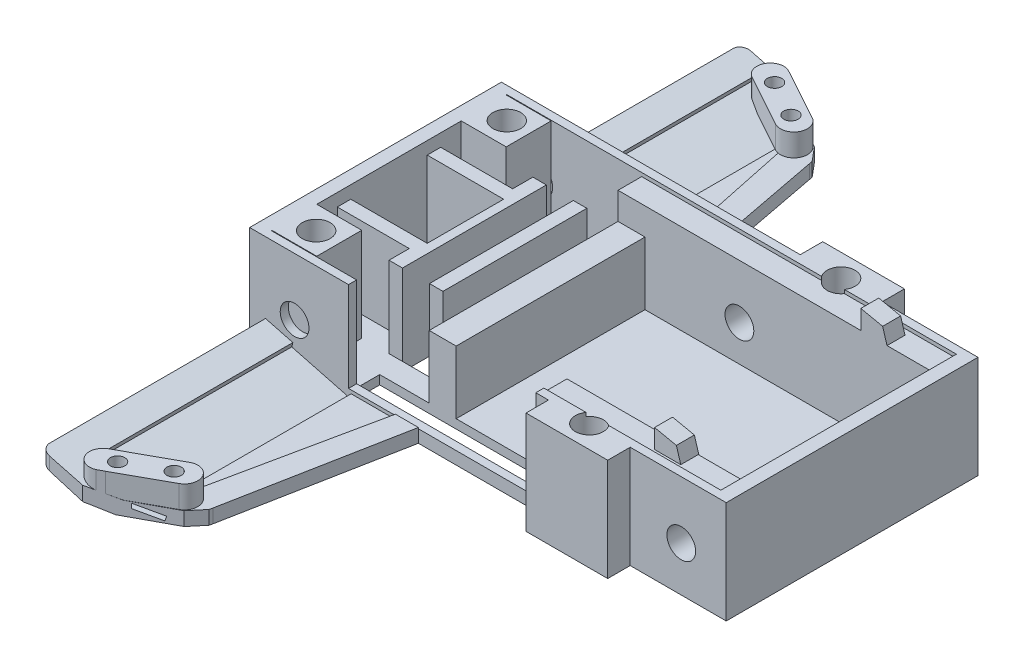
SolidWorks part; units mm, degrees
ref_plane "前视基准面" through (0, 0, 0) normal (0, 0, 1) x (1, 0, 0)
ref_plane "上视基准面" through (0, 0, 0) normal (0, 1, 0) x (1, 0, 0)
ref_plane "右视基准面" through (0, 0, 0) normal (1, 0, 0) x (0, 0, -1)
sketch "草图1" plane through (0, 0, 0) normal (0, 1, 0) x (1, 0, 0)
  line L1 (26.5, -14) -> (-26.5, -14)
  line L2 (26.5, -14) -> (26.5, 14)
  line L3 (26.5, 14) -> (-26.5, 14)
  line L4 (-26.5, -14) -> (-26.5, 14)
  line L5 (26.5, -14) -> (-26.5, 14) construction
  line L6 (26.5, 14) -> (-26.5, -14) construction
  line L7 (25, -13.1) -> (-25, -13.1)
  line L8 (25, -13.1) -> (25, 13.1)
  line L9 (25, 13.1) -> (-25, 13.1)
  line L10 (-25, -13.1) -> (-25, 13.1)
  line L11 (25, -13.1) -> (-25, 13.1) construction
  line L12 (25, 13.1) -> (-25, -13.1) construction
  line L16 (-25, 0.6) -> (-25, 1.6)
  point P0 (0, 0)
  point P6 (0, 0)
  dimension "D1" = 53
  dimension "D2" = 28
  dimension "D3" = 50
  dimension "D4" = 26.2
extrude "凸台-拉伸1" add sketch "草图1" along normal blind 10.4 contours L4 L1 L2 L3 L7 L10 L9 L8 region at (0, 0, 13.4006)
extrude "凸台-拉伸4" add sketch "草图1<3>" against normal blind 1 contours L10 L7 L8 L9 | L4 L1 L2 L3 L7 L10 L9 L8 | L10 region at (0, 0, 13.4006) region at (0, 0, 0)
sketch "草图1<3>" plane through (0, 0, 0) normal (0, 1, 0) x (1, 0, 0) same geometry as "草图1"
sketch "草图2" plane through (0, 0, 0) normal (1, 0, 0) x (0, 0, -1)
  line L0 (-1.6918, 0) -> (1.6918, 0)
  line L1 (1.6918, 0) -> (0.5135, 2.6035)
  line L2 (0.5135, 2.6035) -> (-0.5135, 2.6035)
  line L3 (13.1, 10.4) -> (13.1, 7.6355)
  line L4 (0, 3.9454) -> (0, 2.6035) construction
  line L5 (-1.6918, 0) -> (-0.5135, 2.6035)
  line L6 (0, 0) -> (0, -3.8405) construction
  line L7 (13.1, 7.6355) -> (10.1045, 9.7857)
  line L8 (13.1, 10.4) -> (13.1, 0) construction
  line L9 (10.1045, 9.7857) -> (10.1045, 10.4)
  line L10 (-14, 10.4) -> (14, 10.4) construction
  line L11 (10.1045, 10.4) -> (13.1, 10.4)
  line L12 (-13.1, 10.4) -> (-13.1, 7.6355)
  line L14 (-10.1045, 10.4) -> (-13.1, 10.4)
  line L15 (-10.1045, 9.7857) -> (-10.1045, 10.4)
  line L16 (-13.1, 7.6355) -> (-10.1045, 9.7857)
sketch "草图4" plane through (0, 0, 0) normal (0, 1, 0) x (1, 0, 0)
  line L1 (-12.25, 0) -> (37.6474, -0.075) construction
  line L2 (46.8944, -0.075) -> (20.0243, -0.075) construction
  line L3 (-10, 13.1) -> (-10, -13.1)
  line L4 (25, 10.4681) -> (-7, 10.4681)
  line L6 (25, -10.5319) -> (-7, -10.5319)
  line L7 (25, 13.1) -> (-25, 13.1) construction
  line L8 (-7, 10.4681) -> (-7, -10.5319)
  line L9 (25, 10.4681) -> (-7, -10.5319) construction
  line L10 (25, -10.5319) -> (-7, 10.4681) construction
  line L11 (25, -13.1) -> (-25, -13.1) construction
  line L12 (-10, 13.1) -> (25, 13.1)
  line L13 (25, 13.1) -> (25, 10.4681)
  line L14 (25, -10.5319) -> (25, -13.1)
  line L15 (25, -13.1) -> (-10, -13.1)
  point P4 (9, -0.0319)
  dimension "D1" = 21
  dimension "D2" = 3
extrude "凸台-拉伸7" add sketch "草图4" along normal blind 10 contours L8 L6 L14 L15 L3 L12 L13 L4
sketch "草图3" plane through (0, 0, 14) normal (0, 0, 1) x (1, 0, 0)
  line L0 (26.5, 10.4) -> (26.5, -1) construction
  line L2 (26.5, -1) -> (-26.5, -1) construction
  line L3 (0, 14.561) -> (0, -7.7335) construction
  circle A0 centre (21.5, 4) radius 1.6
  circle A1 centre (-21.5, 4) radius 1.6
  circle A2 centre (3.5, 4) radius 1.6
  dimension "D1" = 5
  dimension "D3" = 3.2
  dimension "D4" = 3.2
  dimension "D5" = 25
  dimension "D2" = 5
extrude "切除-拉伸1" cut sketch "草图3" against normal blind 38
sketch "草图8" plane through (0, 10.4, 0) normal (0, 1, 0) x (1, 0, 0)
  line L1 (-25.7934, -13.0318) -> (-25, -13.0318)
  line L2 (-25.7934, -13.0318) -> (-25.7934, 13.1)
  line L3 (-25.7934, 13.1) -> (-25, 13.1)
  line L4 (-25, -13.0318) -> (-25, 13.1)
  line L5 (25, -13.1) -> (25.8025, -13.1)
  line L6 (25, -13.1) -> (25, 13.1)
  line L7 (25, 13.1) -> (25.8025, 13.1)
  line L8 (25.8025, -13.1) -> (25.8025, 13.1)
sketch "草图9" plane through (-7, 0, 0) normal (1, 0, 0) x (0, 0, -1)
  line L0 (10.4681, 10) -> (10.4681, 0) construction
  line L1 (-10.5319, 10) -> (10.4681, 10)
  line L2 (-10.5319, 10) -> (-10.5319, 7)
  line L3 (-10.5319, 7) -> (10.4681, 7)
  line L4 (10.4681, 10) -> (10.4681, 7)
  dimension "D1" = 3
extrude "切除-拉伸2" cut sketch "草图9" against normal up to next
sketch "草图10" plane through (0, 0, 0) normal (0, 1, 0) x (1, 0, 0)
  line L0 (-19.5511, 0) -> (-1.4893, 0) construction
  line L1 (-10, 13.1) -> (-10, -13.1) construction
  line L2 (-12.5, 8) -> (-15.5, 8)
  line L3 (-12.5, 8) -> (-12.5, -8)
  line L4 (-12.5, -8) -> (-15.5, -8)
  line L5 (-15.5, 8) -> (-15.5, -8)
  line L6 (-12.5, 8) -> (-15.5, -8) construction
  line L7 (-12.5, -8) -> (-15.5, 8) construction
  line L8 (-25, -13.1) -> (-25, 13.1) construction
  line L9 (-12.5, -8) -> (-11, -8)
  line L10 (-12.5, -8) -> (-12.5, 8)
  line L11 (-12.5, 8) -> (-11, 8)
  line L12 (-11, -8) -> (-11, 8)
  line L13 (-15.5, 8) -> (-17, 8)
  line L14 (-15.5, 8) -> (-15.5, -8)
  line L15 (-15.5, -8) -> (-17, -8)
  line L16 (-17, 8) -> (-17, 4.25)
  line L17 (-25, 4.25) -> (-16.5, 4.25)
  line L18 (-25, 4.25) -> (-25, -4.25)
  line L19 (-25, -4.25) -> (-16.5, -4.25)
  line L20 (-16.5, 4.25) -> (-16.5, -4.25)
  line L21 (-25, 4.25) -> (-16.5, -4.25) construction
  line L22 (-25, -4.25) -> (-16.5, 4.25) construction
  line L23 (-17, -4.25) -> (-17, -8)
  line L24 (-25, 4.25) -> (-25, 5.75)
  line L25 (-25, 5.75) -> (-16.5, 5.75)
  line L26 (-25, -4.25) -> (-25, -5.75)
  line L27 (-25, -5.75) -> (-16.5, -5.75)
  line L29 (-18, -2.75) -> (-23.5, -2.75)
  line L30 (-18, -2.75) -> (-18, 2.75)
  line L31 (-18, 2.75) -> (-23.5, 2.75)
  line L32 (-23.5, -2.75) -> (-23.5, 2.75)
  line L33 (-18, -2.75) -> (-23.5, 2.75) construction
  line L34 (-18, 2.75) -> (-23.5, -2.75) construction
  point P3 (-14, 0)
  point P14 (-20.75, 0)
  point P27 (-20.75, 0)
  line M24 (-25, 13.1) -> (-25, -13.1)
  dimension "D1" = 3
  dimension "D2" = 16
  dimension "D3" = 2.5
  dimension "D4" = 1.5
  dimension "D5" = 1.5
  dimension "D6" = 8.5
  dimension "D7" = 8.5
  dimension "D8" = 1.5
  dimension "D9" = 1.5
  dimension "D10" = 5.5
extrude "切除-拉伸3" cut sketch "草图10" against normal up to next contours L32 L29 L30 L31 | L2 L5 L4 L3 region at (-14, 0, 0) region at (-20.75, 0, 0)
extrude "凸台-拉伸9" add sketch "草图10<3>" along normal blind 9 contours L27 L23 L19 M24 | L19 L23 L15 L5 L13 L16 L17 L20 | L25 L17 L16 M24 | L9 L12 L11 L3 region at (-11.75, 0, 0) region at (-16.1424, 0, 0) region at (-21, 0, -5) region at (-21, 0, 5)
sketch "草图10<3>" plane through (0, 0, 0) normal (0, 1, 0) x (1, 0, 0) same geometry as "草图10"
sketch "草图11" plane through (0, 0, -10.4681) normal (0, 0, 1) x (1, 0, 0)
  line L0 (19.9148, 10) -> (19.4253, 11.613)
  line L2 (17, 12.1249) -> (17, 10)
  line L3 (17, 10) -> (19.9148, 10)
  line L4 (19.4253, 11.613) -> (17, 12.1249)
  line L5 (25, 10) -> (-10, 10) construction
  dimension "D1" = 8
extrude "凸台-拉伸10" add sketch "草图11" against normal blind 2
mirror "镜向1" about plane through (0, 0, 0) normal (0, 0, 1) of "凸台-拉伸10"
sketch "草图12" plane through (0, 0, -14) normal (0, 0, -1) x (-1, 0, 0)
  line L0 (7.7325, -1) -> (7.7325, 0.5265)
  line L1 (-26.5, -1) -> (26.5, -1) construction
  line L2 (7.7325, 0.5265) -> (17.1203, 0.5265)
  line L3 (17.1203, 0.5265) -> (24.7311, 2.5211)
  line L4 (24.7311, 2.5211) -> (24.7311, 1.1193)
  line L5 (24.7311, 1.1193) -> (17.675, -1)
  line L6 (17.675, -1) -> (7.7325, -1)
  line L7 (7.7325, 0.5265) -> (7.7325, -0.2367)
  line M11 (-26.5, -1) -> (26.5, -1)
extrude "凸台-拉伸11" add sketch "草图12" along normal blind 25 contours L5 L4 L3 L2 L0 M11 region at (-16.2046, 0.1955, -14)
sketch "草图14" plane through (-0.9711, -3.7055, 0) normal (0.2535, 0.9673, 0) x (0.9673, -0.2535, 0)
  line L0 (-16.6945, 14) -> (-21.4208, 14)
  line L1 (22.998, 14) -> (-28.2708, 14) construction
  line L2 (-21.4208, 14) -> (-21.4208, 37.1066)
  line L3 (-21.4208, 37.1066) -> (-13.4678, 37.1066)
  line L4 (-13.4678, 37.1066) -> (-13.4678, 14)
  line L5 (-13.4678, 14) -> (-16.6945, 14)
extrude "切除-拉伸5" cut sketch "草图14" against normal blind 0.5
sketch "草图15" plane through (0, 0.5265, 0) normal (0, 1, 0) x (1, 0, 0)
  line L0 (-17.1203, 37.1066) -> (-14.6915, 34.9739)
  line L1 (-14.6915, 34.9739) -> (-10.2892, 14)
  line L2 (26.5, 14) -> (-26.5, 14) construction
  line L3 (-10.2892, 14) -> (-17.1203, 14)
  line L4 (-17.1203, 14) -> (-17.1203, 37.1066)
extrude "切除-拉伸6" cut sketch "草图15" against normal blind 0.5 contours L1 L3 L4 L0
fillet "圆角1" radius 1 1 edges at (-24.7311, 1.8202, -39)
sketch "草图16" plane through (0, 0.5265, 0) normal (0, 1, 0) x (1, 0, 0)
  line L0 (-19.6995, 37.1066) -> (-13.8666, 33.8953) construction
  line L1 (-18.976, 38.4206) -> (-13.1431, 35.2094)
  line L2 (-20.4229, 35.7925) -> (-14.59, 32.5813)
  line L3 (-17.1203, 37.1066) -> (-21.6922, 37.1066) construction
  arc A0 (-18.976, 38.4206) -> (-20.4229, 35.7925) centre (-19.6995, 37.1066) ccw
  arc A1 (-14.59, 32.5813) -> (-13.1431, 35.2094) centre (-13.8666, 33.8953) ccw
  circle A3 centre (-18.6523, 36.53) radius 0.8
  circle A4 centre (-14.598, 34.298) radius 0.8
  point P2 (-16.783, 35.5009)
  line M6 (-17.1203, 37.1066) -> (-14.6915, 34.9739)
  line M7 (-14.6915, 34.9739) -> (-10.2892, 14)
  dimension "D1" = 1.5
  dimension "D2" = 1.6
extrude "凸台-拉伸12" add sketch "草图16" along normal blind 2.5
extrude "切除-拉伸7" cut sketch "草图16<2>" against normal blind 5.5 contours A4 L0 M6 | L0 A4 M7 M6 | L0 A4 M6 | L0 A4 M6 M7 | A3 region at (-14.9062, 0.5265, -34.2295) region at (-14.2433, 0.5265, -34.3768)
sketch "草图16<2>" plane through (0, 0.5265, 0) normal (0, 1, 0) x (1, 0, 0) same geometry as "草图16"
sketch "草图13" plane through (0, 0.5265, 0) normal (0, 1, 0) x (1, 0, 0)
  line L0 (-7.7325, 14) -> (-11.3977, 33.1768)
  line L1 (-17.1203, 39) -> (-7.7325, 39)
  line L2 (-7.7325, 39) -> (-7.7325, 14)
  line L3 (-11.4743, 33.5302) -> (-12.7363, 35.0442)
  line L5 (-19.4851, 39) -> (-17.1203, 39)
  line L6 (-12.7363, 35.0442) -> (-20.0597, 39)
  line L8 (-19.4851, 39) -> (-20.0597, 39)
  arc A0 (-11.3977, 33.1768) -> (-11.4743, 33.5302) centre (-18.628, 31.795) ccw
extrude "切除-拉伸4" cut sketch "草图13" along normal mid plane 10
mirror "镜向3" about plane through (0, 0, 0) normal (0, 0, 1) of "切除-拉伸7", "凸台-拉伸11", "切除-拉伸4", "切除-拉伸5", "切除-拉伸6", "圆角1", "凸台-拉伸12"
sketch "草图18" plane through (0, 10.4, 0) normal (0, 1, 0) x (1, 0, 0)
  line L0 (26.5, -14) -> (-26.5, -14) construction
  line L1 (5.3247, -14) -> (-15.5041, -14)
  line L2 (5.3247, -14) -> (5.3247, -10.5319)
  line L3 (5.3247, -10.5319) -> (-15.5041, -10.5319)
  line L4 (-15.5041, -14) -> (-15.5041, -10.5319)
  line L5 (-15.5041, -13.1) -> (5.3247, -13.1)
  line L6 (25, -13.1) -> (-25, -13.1) construction
  line M2 (-26.5, -14) -> (26.5, -14)
  line M5 (25, -13.1) -> (-25, -13.1)
extrude "切除-拉伸8" cut sketch "草图18" against normal blind 10 contours L4 L2 M2 M5 region at (-5.0897, 10.4, 13.55)
extrude "切除-拉伸9" cut sketch "草图18<3>" against normal up to surface (11.4 mm away) contours L4 L2 L3 M5 region at (-5.0897, 10.4, 11.816) up to face at (-14.598, -1, 35.098)
sketch "草图18<3>" plane through (0, 10.4, 0) normal (0, 1, 0) x (1, 0, 0) same geometry as "草图18"
sketch "草图21" plane through (0, -1, 0) normal (0, -1, 0) x (1, 0, 0)
  line L0 (26.5, 14) -> (-7.7325, 14) construction
  line L1 (15.8211, 16.5) -> (6.7328, 16.5)
  line L2 (15.8211, 16.5) -> (15.8211, 14)
  line L3 (15.8211, 14) -> (6.7328, 14)
  line L4 (6.7328, 16.5) -> (6.7328, 14)
  line L5 (17.5645, 0) -> (-8.8715, 0) construction
  line L6 (6.7328, -16.5) -> (6.7328, -14)
  line L7 (15.8211, -16.5) -> (15.8211, -14)
  line L8 (15.8211, -14) -> (6.7328, -14)
  line L9 (15.8211, -16.5) -> (6.7328, -16.5)
  line L10 (-15.5041, 13.1) -> (-25, 13.1) construction
  line L11 (-25, 13.0318) -> (-20, 13.0318)
  line L12 (-25, 13.0318) -> (-25, 8.0318)
  line L13 (-25, 8.0318) -> (-20, 8.0318)
  line L14 (-20, 13.0318) -> (-20, 8.0318)
  line L15 (-25, -13.0318) -> (-25, -8.0318)
  line L16 (-25, -13.0318) -> (-20, -13.0318)
  line L17 (-20, -13.0318) -> (-20, -8.0318)
  line L18 (-25, -8.0318) -> (-20, -8.0318)
  circle A0 centre (11.277, 14) radius 1.55
  circle A1 centre (11.277, -14) radius 1.55
  circle A2 centre (-22.5, 10.6) radius 1.55
  circle A3 centre (-22.5, -10.6) radius 1.55
  dimension "D1" = 3.1
  dimension "D3" = 2.5
  dimension "D2" = 2.5
  dimension "D4" = 2.5
  dimension "D5" = 5
  dimension "D6" = 5
extrude "凸台-拉伸13" add sketch "草图21" against normal up to surface (11.4 mm away) contours L9 L6 L8 L7 | L1 L4 L3 L2 | L13 L14 L11 L12 | L18 L17 L16 L15 up to face at (-1.6966, 10.4, 4.5167)
extrude "切除-拉伸10" cut sketch "草图21<3>" against normal up to surface (11.4 mm away) contours A1 | A3 | A2 | A0 up to face at (-3.9337, 10.4, 1.9357)
sketch "草图21<3>" plane through (0, -1, 0) normal (0, -1, 0) x (1, 0, 0) same geometry as "草图21"
